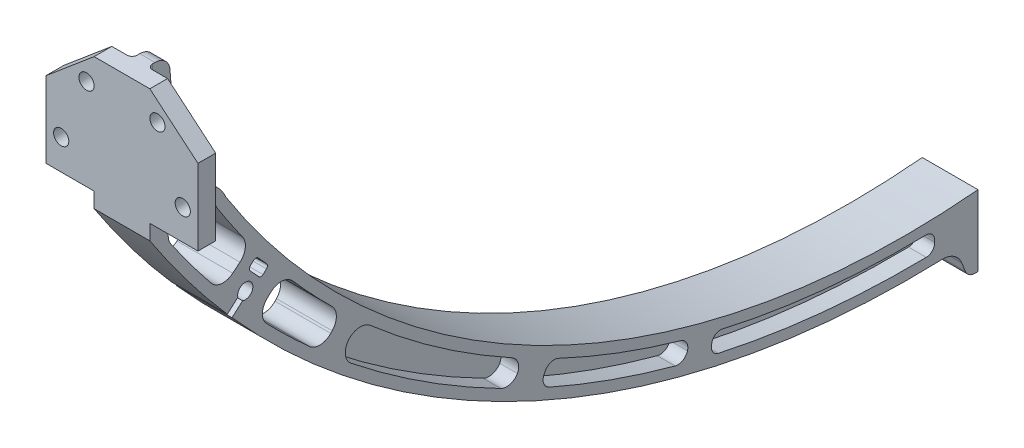
SolidWorks part; units mm, degrees
ref_plane "Alzado" through (0, 0, 0) normal (0, 0, 1) x (1, 0, 0)
ref_plane "Planta" through (0, 0, 0) normal (0, 1, 0) x (1, 0, 0)
ref_plane "Vista lateral" through (0, 0, 0) normal (1, 0, 0) x (0, 0, -1)
sketch "Croquis1" plane through (0, 0, 0) normal (0, 0, 1) x (1, 0, 0)
  line L0 (0, 0) -> (0, 20.7129) construction
  line L1 (5, 0) -> (15, 0)
  line L2 (15, 0) -> (15, 15)
  line L3 (15, 15) -> (5.5, 23)
  line L4 (5.5, 23) -> (-5.5, 23)
  line L5 (-13.9544, 6) -> (23.5839, 6) construction
  line L6 (-13.9544, 18) -> (16.4014, 18) construction
  line L9 (5, 0) -> (-15, 0)
  line L10 (-15, 0) -> (-15, 15)
  line L11 (-15, 15) -> (-5.5, 23)
  circle A0 centre (12, 6) radius 1.5
  circle A1 centre (7, 18) radius 1.5
  circle A2 centre (-12, 6) radius 1.5
  circle A3 centre (-7, 18) radius 1.5
  point P3 (0, 23)
  point P27 (0, 23)
  dimension "D7" = 3
  dimension "D9" = 3
  dimension "D1" = 15
  dimension "D2" = 15
  dimension "D3" = 5.5
  dimension "D4" = 23
  dimension "D5" = 6
  dimension "D6" = 12
  dimension "D8" = 12
  dimension "D10" = 5
extrude "Saliente-Extruir1" add sketch "Croquis1" along normal mid plane 3.5
sketch "Croquis3" plane through (0, 0, 0) normal (1, 0, 0) x (0, 0, -1)
  line L0 (1.75, 0) -> (161.75, 0) construction
  line L1 (161.75, 0) -> (161.75, -80) construction
  line L2 (161.75, -80) -> (1.75, -80) construction
  line L3 (161.75, -76) -> (161.75, -84)
  line L4 (-1.75, 0) -> (-1.75, -3)
  line L5 (-1.75, -3) -> (13.25, -3) construction
  line L6 (161.75, -84) -> (161.75, -90)
  line L7 (161.75, -90) -> (159.75, -90)
  line L8 (159.75, -90) -> (157.5078, -84.2614)
  line L9 (1.75, 0) -> (-1.75, 0)
  arc A0 (0, 0) -> (161.75, -80) centre (149.9254, 99.6112) ccw construction
  arc A1 (161.75, -76) -> (13.25, -3) centre (147.2385, 82.0228) cw
  arc A2 (-1.75, -3) -> (157.5078, -84.2614) centre (148.5938, 94.9579) ccw
  arc A3 (13.25, -3) -> (1.75, 0) centre (6.3476, -5.9176) ccw
  point P11 (161.75, -80)
  point P14 (0, 0)
  dimension "D3" = 180
  dimension "D1" = 160
  dimension "D2" = 80
  dimension "D4" = 8
  dimension "D5" = 3
  dimension "D6" = 15
  dimension "D8" = 6
  dimension "D9" = 2
extrude "Saliente-Extruir2" add sketch "Croquis3" along normal mid plane 11
fillet "Redondeo1" radius 2 1 edges at (0, -90, -159.75)
fillet "Redondeo2" radius 4 1 edges at (0, -84.2614, -157.5078)
sketch "Croquis4" plane through (5.5, 0, 0) normal (1, 0, 0) x (0, 0, -1)
  line L0 (12.2937, -18.6534) -> (18.1977, -13.7322)
  line L1 (15.5039, -22.3976) -> (13.25, -24.385) construction
  line L2 (15.6339, -21.3497) -> (12.787, -23.86)
  line L3 (16.5598, -22.3998) -> (13.713, -24.9101)
  line L4 (17.0919, -20.9974) -> (13.25, -24.385) construction
  line L5 (17.5549, -21.5224) -> (13.713, -24.9101) construction
  line L6 (16.6289, -20.4723) -> (12.787, -23.86) construction
  line L7 (13.713, -24.9101) -> (12.787, -23.86)
  line L8 (17.0919, -20.9974) -> (23.7254, -15.028) construction
  line L9 (20.1485, -20.3319) -> (17.6391, -17.5696)
  line L10 (17.6391, -17.5696) -> (19.2124, -16.1403)
  line L11 (19.2124, -16.1403) -> (21.7218, -18.9026)
  line L12 (21.7218, -18.9026) -> (20.1485, -20.3319)
  line L13 (19.2124, -26.474) -> (24.4171, -21.5892)
  line L14 (31.9627, -38.7673) -> (36.2995, -34.223)
  arc A0 (13.25, -3) -> (161.75, -76) centre (147.2385, 82.0228) ccw construction
  arc A1 (13.25, -3) -> (1.75, 0) centre (6.3476, -5.9176) ccw construction
  arc A2 (13.25, -3) -> (22.5282, -16.1053) centre (147.2385, 82.0228) ccw
  arc A3 (13.25, -3) -> (1.75, 0) centre (6.3476, -5.9176) ccw
  arc A4 (11.4653, -3.9201) -> (18.1977, -13.7322) centre (147.2385, 82.0228) ccw
  arc A5 (11.4653, -3.9201) -> (1.2396, -3.8954) centre (6.3476, -5.9176) ccw
  arc A6 (-1.75, -3) -> (154.6857, -84.3795) centre (148.5938, 94.9579) ccw construction
  arc A7 (-1.75, -3) -> (14.4678, -24.2445) centre (148.5938, 94.9579) ccw
  arc A8 (1.2396, -3.8954) -> (12.2937, -18.6534) centre (148.5938, 94.9579) ccw
  arc A9 (11.4653, -3.9201) -> (2.9771, -1.5793) centre (6.3476, -5.9176) ccw construction
  arc A10 (-1.75, -3) -> (154.6857, -84.3795) centre (148.5938, 94.9579) ccw construction
  arc A11 (16.5598, -22.3998) -> (15.6339, -21.3497) centre (17.0919, -20.9974) ccw
  arc A12 (-0.0743, -1.9082) -> (154.6178, -82.3807) centre (148.5938, 94.9579) ccw construction
  arc A13 (11.4653, -3.9201) -> (161.9329, -77.9916) centre (147.2385, 82.0228) ccw construction
  arc A14 (13.25, -3) -> (161.75, -76) centre (147.2385, 82.0228) ccw construction
  arc A15 (15.0419, -21.8717) -> (15.9679, -22.9217) centre (148.5938, 94.9579) ccw
  arc A16 (19.2124, -26.474) -> (31.9627, -38.7673) centre (148.5938, 94.9579) ccw
  arc A17 (24.4171, -21.5892) -> (36.2995, -34.223) centre (147.2385, 82.0228) ccw
  arc M3 (-1.75, -3) -> (154.6857, -84.3795) centre (148.5938, 94.9579) ccw
  dimension "D3" = 3
  dimension "D1" = 2
  dimension "D2" = 2
  dimension "D4" = 0.7
  dimension "D5" = 0.7
extrude "Cortar-Extruir1" cut sketch "Croquis4" against normal mid plane 25 contours A5 A8 L0 A4 | L12 L11 L10 L9 | L2 A15 L3 A11 | A15 L2 L3 M3 | A17 L13 A16 L14 region at (5.5, -8.7727, -9.6493) region at (5.5, -21.1357, -16.935) region at (5.5, -23.0587, -14.7542) region at (5.5, -18.2361, -19.6805) region at (5.5, -30.2456, -27.7255)
fillet "Redondeo3" radius 3 4 edges at (0, -21.5892, -24.4171) (0, -26.474, -19.2124) (0, -34.223, -36.2995) (0, -38.7673, -31.9627)
fillet "Redondeo4" radius 3 3 edges at (0, -3.8954, -1.2396) (0, -18.6534, -12.2937) (0, -13.7322, -18.1977)
fillet "Redondeo5" radius 0.6 4 edges at (0, -20.3319, -20.1485) (0, -16.1403, -19.2124) (0, -17.5696, -17.6391) (0, -18.9026, -21.7218)
sketch "Croquis5" plane through (5.5, 0, 0) normal (1, 0, 0) x (0, 0, -1)
  line L0 (153.2622, -82.4215) -> (153.1206, -78.5572)
  line L1 (103.8838, -76.7578) -> (104.9125, -72.9903)
  line L2 (109.3786, -74.1411) -> (108.9884, -78.0064)
  line L3 (75.1919, -66.5891) -> (77.1407, -62.5692)
  line L4 (35.4917, -41.7651) -> (39.5644, -37.2535)
  line L5 (69.765, -64.0115) -> (71.9323, -59.9262)
  arc A1 (75.1919, -66.5891) -> (103.8838, -76.7578) centre (148.5938, 94.9579) ccw
  arc A2 (35.4917, -41.7651) -> (69.765, -64.0115) centre (148.5938, 94.9579) ccw
  arc A4 (77.1407, -62.5692) -> (104.9125, -72.9903) centre (147.2385, 82.0228) ccw
  arc A5 (39.5644, -37.2535) -> (71.9323, -59.9262) centre (147.2385, 82.0228) ccw
  arc A6 (108.9884, -78.0064) -> (154.6178, -82.3807) centre (148.5938, 94.9579) ccw
  arc A7 (109.3786, -74.1411) -> (153.1206, -78.5572) centre (147.2385, 82.0228) ccw
extrude "Cortar-Extruir2" cut sketch "Croquis5" against normal blind 3.5 contours A7 L2 A6 L0 | A4 L3 A1 L1 | A5 L4 A2 L5 region at (5.5, -79.2481, -131.1055) region at (5.5, -70.0375, -89.8079) region at (5.5, -50.898, -52.9711)
mirror "Simetría1" about plane through (0, 0, 0) normal (1, 0, 0) of "Cortar-Extruir2"
fillet "Redondeo7" radius 1.7 8 edges at (-3.75, -78.0064, -108.9884) (-3.75, -74.1411, -109.3786) (-3.75, -82.4215, -153.2622) (-3.75, -78.5572, -153.1206) (3.75, -82.4215, -153.2622) (3.75, -78.5572, -153.1206) (3.75, -74.1411, -109.3786) (3.75, -78.0064, -108.9884)
fillet "Redondeo8" radius 2 8 edges at (-3.75, -76.7578, -103.8838) (-3.75, -66.5891, -75.1919) (-3.75, -62.5692, -77.1407) (-3.75, -72.9903, -104.9125) (3.75, -62.5692, -77.1407) (3.75, -66.5891, -75.1919) (3.75, -76.7578, -103.8838) (3.75, -72.9903, -104.9125)
fillet "Redondeo9" radius 2.5 4 edges at (-3.75, -64.0115, -69.765) (-3.75, -59.9262, -71.9323) (3.75, -64.0115, -69.765) (3.75, -59.9262, -71.9323)
fillet "Redondeo10" radius 3 4 edges at (-3.75, -37.2535, -39.5644) (-3.75, -41.7651, -35.4917) (3.75, -37.2535, -39.5644) (3.75, -41.7651, -35.4917)
sketch "Croquis6" plane through (0, 0, 0) normal (1, 0, 0) x (0, 0, -1)
  line L0 (1.75, 23) -> (3.2615, 23)
  line L1 (12.3004, -1.3657) -> (12.3349, -1.3379)
  line L2 (12.3349, -1.3379) -> (9.7077, 3.0002)
  line L3 (1.75, 0) -> (1.75, 23)
  arc A2 (3.2615, 23) -> (6.2099, 20.5544) centre (3.2615, 20) cw
  arc A3 (8.2029, 6.6331) -> (6.2099, 20.5544) centre (77.5101, 23.6587) cw
  arc A4 (8.2029, 6.6331) -> (9.7077, 3.0002) centre (20.8275, 9.7344) ccw
  arc A5 (12.3004, -1.3657) -> (1.75, 0) centre (6.3476, -5.9176) ccw
  point P9 (5.75, 23)
  dimension "D2" = 3
  dimension "D3" = 13
  dimension "D1" = 4
extrude "Saliente-Extruir3" add sketch "Croquis6" along normal mid plane 3
sketch "Croquis7" plane through (1.5, 0, 0) normal (1, 0, 0) x (0, 0, -1)
  line L0 (1.75, 5.3) -> (1.75, 0)
  line L3 (-8.25, 0) -> (-8.25, 15)
  line L4 (-8.25, 0) -> (-8.25, 15)
  line L5 (1.75, 23) -> (1.75, 0) construction
  line L6 (4.75, 5.3) -> (4.75, 1.4038)
  arc A0 (12.3004, -1.3657) -> (1.75, 0) centre (6.3476, -5.9176) ccw construction
  arc A1 (4.75, 1.4038) -> (1.75, 0) centre (6.3476, -5.9176) ccw
  arc A2 (4.75, 1.4038) -> (1.75, 5.3) centre (-19.775, -14.3771) ccw
  line M3 (1.75, 23) -> (1.75, 0)
  arc M4 (1.75, 0) -> (12.3004, -1.3657) centre (6.3476, -5.9176) cw
  dimension "D2" = 3
  dimension "D3" = 5.3
  dimension "D1" = 10
extrude "Saliente-Extruir5" add sketch "Croquis7" along normal up to surface (4 mm away) contours A2 M4 M3 region at (1.5, 2.3603, -2.7486) up to face at (5.5, -46.0708, -72.467)
sketch "Croquis8" plane through (-1.5, 0, 0) normal (-1, 0, 0) x (0, 0, 1)
  line L0 (-4.75, 5.3) -> (-4.75, 1.4038) construction
  line L2 (-1.75, 0) -> (-1.75, 5.3)
  line L3 (-1.75, 23) -> (-1.75, 0) construction
  line L4 (-1.75, 5.3) -> (-4.75, 5.3) construction
  arc A0 (-1.75, 5.3) -> (-4.75, 1.4038) centre (8.5295, -5.7181) ccw
  arc A2 (-1.75, 0) -> (-12.3004, -1.3657) centre (-6.3476, -5.9176) ccw construction
  arc A3 (-1.75, 0) -> (-12.3004, -1.3657) centre (-6.3476, -5.9176) ccw
  line M4 (-1.75, 0) -> (-1.75, 23)
  arc M11 (-12.3004, -1.3657) -> (-1.75, 0) centre (-6.3476, -5.9176) cw
  dimension "D3" = 5.3
  dimension "D4" = 3
extrude "Saliente-Extruir6" add sketch "Croquis8" along normal up to surface (4 mm away) contours A0 M4 M11 region at (-1.5, 2.4022, -2.7722) up to face at (-5.5, -69.1934, -88.1989)
fillet "Redondeo12" radius 1.7 1 edges at (5.5, 2.65, -1.75)
fillet "Redondeo14" radius 1.7 1 edges at (-5.5, 2.65, -1.75)
fillet "Redondeo15" radius 1 3 edges at (1.5, 1.1178, -8.9282) (1.5, 3.4153, -3.3323) (1.5, 14.15, -1.75)
fillet "Redondeo16" radius 1 3 edges at (-1.5, 1.1178, -8.9282) (-1.5, 3.4751, -3.41) (-1.5, 14.15, -1.75)
